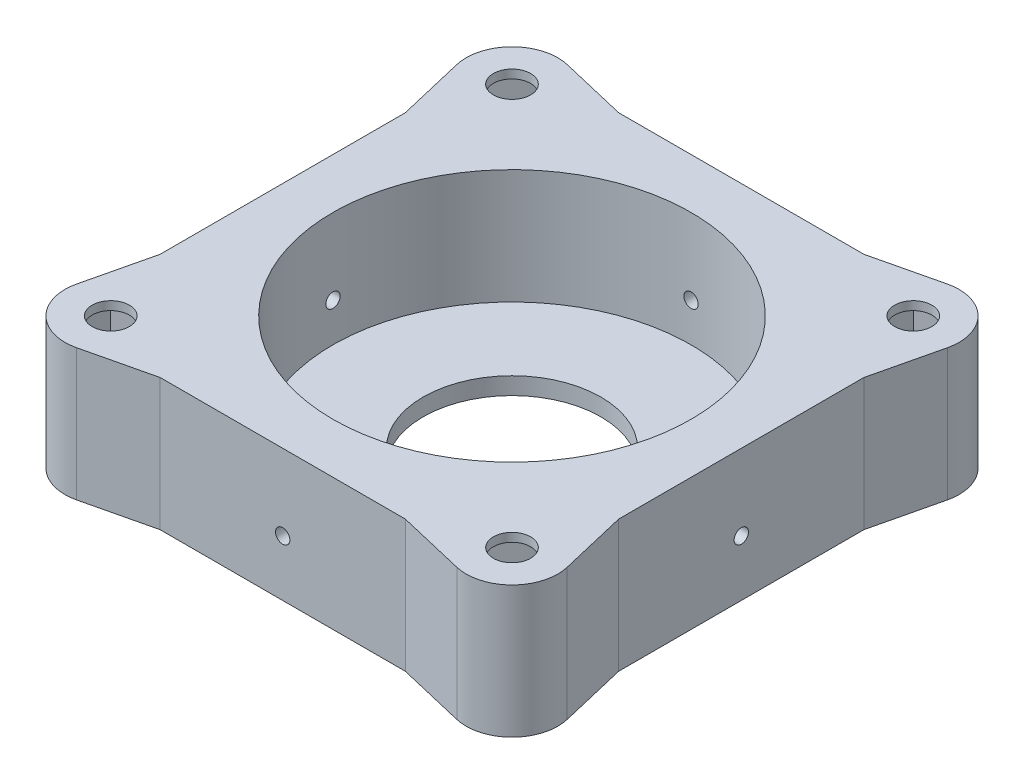
SolidWorks part; units mm, degrees
ref_plane "Front Plane" through (0, 0, 0) normal (0, 0, 1) x (1, 0, 0)
ref_plane "Top Plane" through (0, 0, 0) normal (0, 1, 0) x (1, 0, 0)
ref_plane "Right Plane" through (0, 0, 0) normal (1, 0, 0) x (0, 0, -1)
sketch "Sketch1" plane through (0, 0, 0) normal (0, 1, 0) x (1, 0, 0)
  line L0 (0, 35) -> (0, -35) construction
  line L1 (35, -35) -> (-35, -35)
  line L2 (35, -35) -> (35, 35)
  line L3 (35, 35) -> (-35, 35)
  line L4 (-35, -35) -> (-35, 35)
  line L5 (35, -35) -> (-35, 35) construction
  line L6 (35, 35) -> (-35, -35) construction
  line L7 (-35, 0) -> (35, 0) construction
  line L8 (-33.1578, 42.785) -> (7.8292, 33.0863)
  line L9 (-42.785, 33.1578) -> (-33.0863, -7.8292)
  line L10 (42.785, 33.1578) -> (33.0863, -7.8292)
  line L11 (33.1578, 42.785) -> (-7.8292, 33.0863)
  line L12 (-42.785, -33.1578) -> (-33.0863, 7.8292)
  line L13 (-33.1578, -42.785) -> (7.8292, -33.0863)
  line L14 (33.1578, -42.785) -> (-7.8292, -33.0863)
  line L15 (42.785, -33.1578) -> (33.0863, 7.8292)
  line L17 (40, -40) -> (-40, -40)
  line L18 (40, -40) -> (40, 40)
  line L19 (40, 40) -> (-40, 40)
  line L20 (-40, -40) -> (-40, 40)
  line L21 (40, -40) -> (-40, 40) construction
  line L22 (40, 40) -> (-40, -40) construction
  circle A0 centre (0, 0) radius 15.5
  circle A1 centre (0, 0) radius 34
  circle A2 centre (-35, 35) radius 3.25
  circle A3 centre (0, 0) radius 40
  circle A4 centre (-35, 35) radius 8
  circle A5 centre (35, 35) radius 3.25
  circle A6 centre (35, 35) radius 8
  circle A7 centre (-35, -35) radius 3.25
  circle A8 centre (-35, -35) radius 8
  circle A9 centre (35, -35) radius 3.25
  circle A10 centre (35, -35) radius 8
  dimension "D1" = 31
  dimension "D2" = 68
  dimension "D3" = 6.5
  dimension "D5" = 80
  dimension "D4" = 16
  dimension "D6" = 70
extrude "Boss-Extrude1" add sketch "Sketch1" along normal blind 19.5 contours L19 A4 L20 | L3 A4 L19 L20 L4 A2 | L4 A4 L3 A2 | A4 L9 L20 | A4 L20 L9 A3 L4 | A3 L9 L20 | L4 A3 L9 | L9 A3 L12 L4 | A3 L20 L12 | L12 A3 L4 | L20 A8 L4 A3 L12 | L12 A8 L20 | A8 L17 L20 | A8 L20 L17 L1 A7 L4 | A8 L4 A7 L1 | L4 A8 L1 A3 | L4 A3 L1 L13 L14 A1 L9 L12 | L3 A3 L4 L9 L12 A1 L11 L8 | A1 L12 L9 | A4 L4 A3 L3 | A4 L3 A3 L8 L19 | A4 L19 L8 | A3 L19 L8 | L8 A3 L3 | L11 A3 L8 L3 | A1 L8 L11 | L3 A3 L11 | L2 A3 L3 L11 L8 A1 L15 L10 | L3 A6 L19 L11 A3 | A3 L11 L19 | L19 A6 L11 | L2 A6 L3 A3 | A6 L2 A5 L3 | A6 L3 A5 L2 L18 L19 | A6 L19 L18 | L10 A6 L18 | L18 A6 L2 A3 L10 | A3 L18 L10 | L10 A3 L2 | L15 A3 L10 L2 | A3 L15 L18 | L2 A3 L15 | A1 L10 L15 | L1 A3 L2 L15 L10 A1 L13 L14 | A10 L18 L15 A3 L2 | A10 L15 L18 | A10 L2 A3 L1 | L18 A10 L2 A9 L1 L17 | L2 A10 L1 A9 | A10 L18 L17 | A10 L17 L14 | A10 L1 A3 L14 L17 | L14 A3 L1 | A3 L17 L14 | A3 L14 L1 L13 | A1 L14 L13 | L1 A3 L13 | A3 L13 L17 | L1 A8 L17 L13 A3 | L17 A8 L13 | A1 A0 region at (-27.625, 0, 37.5886) region at (-28.9419, 0, 28.9419) region at (-31.2062, 0, 31.2062) region at (-21.8672, 0, 37.555) region at (-24.6184, 0, 24.6184) region at (-10.9152, 0, 35.995) region at (-37.555, 0, 21.8672) region at (-30.8311, 0, 41.5907) region at (-27.2274, 0, 40.8217) region at (0, 0, 37.8149) region at (-35.995, 0, 10.9152) region at (-12.614, 0, 39.3478) region at (-40.8217, 0, 27.2274) region at (24.6184, 0, 24.6184) region at (10.9152, 0, 35.995) region at (0, 0, 34.191) region at (-37.8149, 0, 0) region at (-39.3478, 0, 12.614) region at (12.614, 0, 39.3478) region at (28.9419, 0, 28.9419) region at (21.8672, 0, 37.555) region at (0, 0, 33.0383) region at (-35.995, 0, -10.9152) region at (-24.6184, 0, -24.6184) region at (-34.191, 0, 0) region at (-39.3478, 0, -12.614) region at (27.2274, 0, 40.8217) region at (31.2062, 0, 31.2062) region at (29.375, 0, 35.1838) region at (37.555, 0, 21.8672) region at (35.995, 0, 10.9152) region at (34.191, 0, 0) region at (-37.555, 0, -21.8672) region at (-28.9419, 0, -28.9419) region at (-40.8217, 0, -27.2274) region at (30.8311, 0, 41.5907) region at (37.8149, 0, 0) region at (39.3478, 0, 12.614) region at (24.6184, 0, -24.6184) region at (-37.5886, 0, -27.625) region at (-31.2062, 0, -31.2062) region at (-10.9152, 0, -35.995) region at (-21.8672, 0, -37.555) region at (0, 0, -34.191) region at (-40.5144, 0, -40.5144) region at (40.8217, 0, 27.2274) region at (35.995, 0, -10.9152) region at (39.3478, 0, -12.614) region at (0, 0, -37.8149) region at (-12.614, 0, -39.3478) region at (-27.2274, 0, -40.8217) region at (28.9419, 0, -28.9419) region at (37.555, 0, -21.8672) region at (40.8217, 0, -27.2274) region at (10.9152, 0, -35.995) region at (12.614, 0, -39.3478) region at (31.2062, 0, -31.2062) region at (35.1838, 0, -29.375) region at (21.8672, 0, -37.555) region at (41.5907, 0, -30.8311)
sketch "Sketch2" plane through (0, 19.5, 0) normal (0, 1, 0) x (1, 0, 0)
  circle A0 centre (0, 0) radius 31.25
  dimension "D1" = 62.5
extrude "Cut-Extrude1" cut sketch "Sketch2" against normal blind 16.5
sketch "Sketch3" plane through (0, 0, 0) normal (0, -1, 0) x (1, 0, 0)
  circle A0 centre (-35, 35) radius 5
  circle A1 centre (35, 35) radius 5
  circle A2 centre (35, -35) radius 5
  circle A3 centre (-35, -35) radius 5
  dimension "D1" = 10
extrude "Cut-Extrude2" cut sketch "Sketch3" against normal blind 6
sketch "Sketch4" plane through (0, 0, 40) normal (0, 0, 1) x (1, 0, 0)
  line L0 (0, 0) -> (0, 19.5) construction
  line L1 (21.3883, 0) -> (-21.3883, 0) construction
  line L2 (21.3883, 19.5) -> (-21.3883, 19.5) construction
  circle A0 centre (0, 9.75) radius 1.25
  dimension "D1" = 2.5
extrude "Cut-Extrude3" cut sketch "Sketch4" against normal up to surface (80 mm away) up to face at (0, 9.75, -40)
sketch "Sketch5" plane through (40, 0, 0) normal (1, 0, 0) x (0, 0, -1)
  line L0 (0, 0) -> (0, 19.5) construction
  line L1 (-21.3883, 19.5) -> (21.3883, 19.5) construction
  circle A0 centre (0, 9.75) radius 1.25
  dimension "D1" = 2.5
extrude "Cut-Extrude4" cut sketch "Sketch5" against normal up to surface (80 mm away) up to face at (-40, 9.75, 0)
sketch "Sketch6" plane through (0, 19.5, 0) normal (0, 1, 0) x (1, 0, 0)
  line L12 (21.3883, -40) -> (33.1578, -42.785)
  line L13 (42.785, -33.1578) -> (40, -21.3883)
  line L14 (40, -21.3883) -> (40, 21.3883)
  line L15 (40, 21.3883) -> (42.785, 33.1578)
  line L16 (33.1578, 42.785) -> (21.3883, 40)
  line L17 (21.3883, 40) -> (-21.3883, 40)
  line L18 (-21.3883, 40) -> (-33.1578, 42.785)
  line L19 (-42.785, 33.1578) -> (-40, 21.3883)
  line L20 (-40, 21.3883) -> (-40, -21.3883)
  line L21 (-40, -21.3883) -> (-42.785, -33.1578)
  line L22 (-33.1578, -42.785) -> (-21.3883, -40)
  line L23 (-21.3883, -40) -> (21.3883, -40)
  line L24 (21.3883, -40) -> (33.1578, -42.785)
  line L25 (42.785, -33.1578) -> (40, -21.3883)
  line L26 (40, -21.3883) -> (40, 21.3883)
  line L27 (40, 21.3883) -> (42.785, 33.1578)
  line L28 (33.1578, 42.785) -> (21.3883, 40)
  line L29 (21.3883, 40) -> (-21.3883, 40)
  line L30 (-21.3883, 40) -> (-33.1578, 42.785)
  line L31 (-42.785, 33.1578) -> (-40, 21.3883)
  line L32 (-40, 21.3883) -> (-40, -21.3883)
  line L33 (-40, -21.3883) -> (-42.785, -33.1578)
  line L34 (-33.1578, -42.785) -> (-21.3883, -40)
  line L35 (-21.3883, -40) -> (21.3883, -40)
  circle A0 centre (0, 0) radius 31.25 construction
  circle A1 centre (35, 35) radius 3.25 construction
  circle A2 centre (-35, 35) radius 3.25 construction
  circle A3 centre (35, -35) radius 3.25 construction
  arc A4 (33.1578, -42.785) -> (42.785, -33.1578) centre (35, -35) ccw
  arc A5 (42.785, 33.1578) -> (33.1578, 42.785) centre (35, 35) ccw
  arc A6 (-33.1578, 42.785) -> (-42.785, 33.1578) centre (-35, 35) ccw
  arc A7 (-42.785, -33.1578) -> (-33.1578, -42.785) centre (-35, -35) ccw
  arc A8 (33.1578, -42.785) -> (42.785, -33.1578) centre (35, -35) ccw
  arc A9 (42.785, 33.1578) -> (33.1578, 42.785) centre (35, 35) ccw
  arc A10 (-33.1578, 42.785) -> (-42.785, 33.1578) centre (-35, 35) ccw
  arc A11 (-42.785, -33.1578) -> (-33.1578, -42.785) centre (-35, -35) ccw
  circle A12 centre (-35, -35) radius 3.25 construction
  circle A13 centre (0, 0) radius 31.25
  circle A14 centre (35, 35) radius 3.25
  circle A15 centre (-35, 35) radius 3.25
  circle A16 centre (35, -35) radius 3.25
  circle A17 centre (-35, -35) radius 3.25
  dimension "D1" = 0
extrude "Boss-Extrude4" add sketch "Sketch6" along normal blind 3.5
sketch "Sketch7" plane through (0, 0, 0) normal (0, -1, 0) x (1, 0, 0)
  line L0 (-35, 35) -> (-38.7123, 38.7123) construction
  line L1 (-29.1444, 33.431) -> (-30.7134, 39.2866)
  line L2 (-30.7134, 39.2866) -> (-36.569, 40.8556)
  line L3 (-36.569, 40.8556) -> (-40.8556, 36.569)
  line L4 (-40.8556, 36.569) -> (-39.2866, 30.7134)
  line L5 (-39.2866, 30.7134) -> (-33.431, 29.1444)
  line L6 (-33.431, 29.1444) -> (-29.1444, 33.431)
  line L7 (39.2866, 30.7134) -> (40.8556, 36.569)
  line L8 (40.8556, 36.569) -> (36.569, 40.8556)
  line L9 (36.569, 40.8556) -> (30.7134, 39.2866)
  line L10 (30.7134, 39.2866) -> (29.1444, 33.431)
  line L11 (29.1444, 33.431) -> (33.431, 29.1444)
  line L12 (33.431, 29.1444) -> (39.2866, 30.7134)
  line L13 (30.7134, -39.2866) -> (36.569, -40.8556)
  line L14 (36.569, -40.8556) -> (40.8556, -36.569)
  line L15 (40.8556, -36.569) -> (39.2866, -30.7134)
  line L16 (39.2866, -30.7134) -> (33.431, -29.1444)
  line L17 (33.431, -29.1444) -> (29.1444, -33.431)
  line L18 (29.1444, -33.431) -> (30.7134, -39.2866)
  line L19 (-39.2866, -30.7134) -> (-40.8556, -36.569)
  line L20 (-40.8556, -36.569) -> (-36.569, -40.8556)
  line L21 (-36.569, -40.8556) -> (-30.7134, -39.2866)
  line L22 (-30.7134, -39.2866) -> (-29.1444, -33.431)
  line L23 (-29.1444, -33.431) -> (-33.431, -29.1444)
  line L24 (-33.431, -29.1444) -> (-39.2866, -30.7134)
  line L25 (0, 40) -> (0, -40) construction
  line L26 (21.3883, 40) -> (-21.3883, 40) construction
  line L27 (21.3883, -40) -> (-21.3883, -40) construction
  circle A0 centre (-35, 35) radius 5.25 construction
  point P32 (0, 0)
  dimension "D1" = 10.5
  dimension "D2" = 4
extrude "Cut-Extrude5" cut sketch "Sketch7" against normal offset from surface (21.5 mm away) 1.5 up to face at (35, 23, 38.25)
